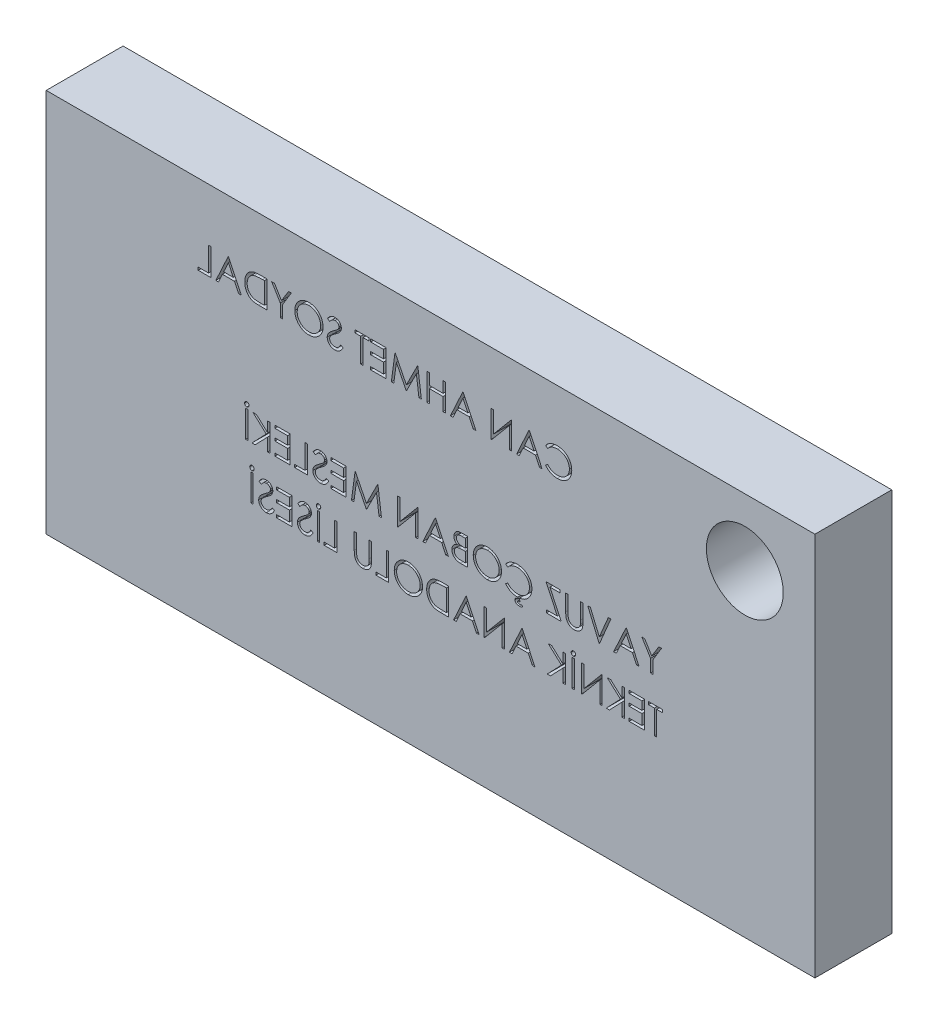
SolidWorks part; units mm, degrees
ref_plane "Ön Düzlem" through (0, 0, 0) normal (0, 0, 1) x (1, 0, 0)
ref_plane "Üst Düzlem" through (0, 0, 0) normal (0, 1, 0) x (1, 0, 0)
ref_plane "Sağ Düzlem" through (0, 0, 0) normal (1, 0, 0) x (0, 0, -1)
sketch "Çizim1" plane through (0, 0, 0) normal (0, 0, 1) x (1, 0, 0)
  line L0 (0, 0) -> (100, 0)
  line L1 (100, 0) -> (100, 50)
  line L2 (100, 50) -> (0, 50)
  line L3 (0, 50) -> (0, 0)
  dimension "D1" = 100
  dimension "D2" = 50
  dimension "D3" = 100
  dimension "D4" = 50
extrude "Yükseklik-Ekstrüzyon1" add sketch "Çizim1" along normal blind 10 contours L3 L0 L1 L2
sketch "Çizim2" plane through (0, 0, 0) normal (0, 0, -1) x (-1, 0, 0)
  circle A0 centre (-90.8834, 41.3294) radius 5
sketch "Çizim3" plane through (0, 0, 0) normal (0, 0, -1) x (-1, 0, 0)
extrude "Kes-Ekstrüzyon1" cut sketch "Çizim2" against normal blind 10
sketch "Çizim4" plane through (0, 0, 0) normal (0, 0, -1) x (-1, 0, 0)
  text T0 "CAN AHMET SOYDAL"
extrude "Kes-Ekstrüzyon2" cut sketch "Çizim4" against normal blind 10
sketch "Çizim9" plane through (0, 0, 0) normal (0, 0, -1) x (-1, 0, 0)
  text T0 "YAVUZ ÇOBAN MESLEKİ \r\nTEKNİK ANADOLU LİSESİ\r\n"
extrude "Kes-Ekstrüzyon3" cut sketch "Çizim9" against normal blind 10
